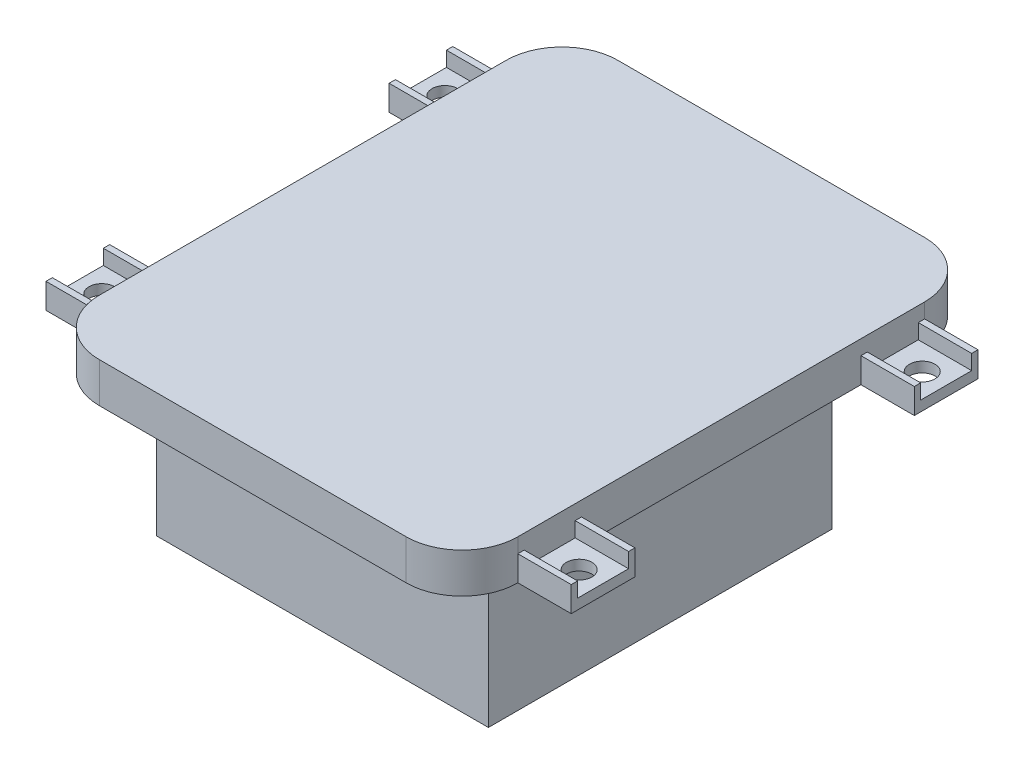
SolidWorks part; units mm, degrees
ref_plane "Front Plane" through (0, 0, 0) normal (0, 0, 1) x (1, 0, 0)
ref_plane "Top Plane" through (0, 0, 0) normal (0, 1, 0) x (1, 0, 0)
ref_plane "Right Plane" through (0, 0, 0) normal (1, 0, 0) x (0, 0, -1)
sketch "Sketch1" plane through (0, 0, 0) normal (0, 1, 0) x (1, 0, 0)
  line L0 (-32.915, 25.49) -> (-32.915, 32.49) construction
  line L1 (-32.915, -32.49) -> (32.915, -32.49) construction
  line L2 (-32.915, 17.51) -> (-32.915, 25.49)
  line L3 (-19.2233, 32.49) -> (32.915, 32.49) construction
  line L4 (32.915, -32.49) -> (32.915, 32.49) construction
  line L5 (-32.915, -32.49) -> (32.915, 32.49) construction
  line L6 (-25.8234, 25.49) -> (32.915, -32.49) construction
  line L7 (-32.915, 17.51) -> (-26.2233, 17.51)
  line L8 (-32.915, 17.51) -> (-32.915, 25.49)
  line L9 (-32.915, 25.49) -> (-26.2233, 25.49)
  line L10 (-26.2233, 17.51) -> (-26.2233, 25.49)
  line L11 (-32.915, 32.49) -> (-25.8234, 25.49) construction
  line L12 (-32.915, 32.49) -> (-19.2233, 32.49) construction
  line L13 (-26.2233, 17.51) -> (-26.2233, -17.51)
  line L14 (-32.915, -32.49) -> (-32.915, 17.51) construction
  line L15 (-19.2233, 32.49) -> (19.2233, 32.49)
  line L16 (0, 0) -> (0, 32.49) construction
  line L17 (0, 0) -> (26.2233, 0) construction
  line L18 (26.2233, 17.51) -> (26.2233, -17.51)
  line L19 (32.915, 25.49) -> (26.2233, 25.49)
  line L20 (26.2233, 17.51) -> (26.2233, 25.49)
  line L21 (32.915, 17.51) -> (26.2233, 17.51)
  line L22 (32.915, 17.51) -> (32.915, 25.49)
  line L23 (32.915, -17.51) -> (32.915, -25.49)
  line L24 (32.915, -25.49) -> (26.2233, -25.49)
  line L25 (32.915, -17.51) -> (26.2233, -17.51)
  line L26 (26.2233, -17.51) -> (26.2233, -25.49)
  line L27 (-19.2233, -32.49) -> (19.2233, -32.49)
  line L28 (-26.2233, -17.51) -> (-26.2233, -25.49)
  line L29 (-32.915, -25.49) -> (-26.2233, -25.49)
  line L30 (-32.915, -17.51) -> (-32.915, -25.49)
  line L31 (-32.915, -17.51) -> (-26.2233, -17.51)
  circle A0 centre (-29.915, 21.5) radius 1.6
  arc A1 (-26.2233, 25.49) -> (-19.2233, 32.49) centre (-19.2233, 25.49) cw
  circle A3 centre (29.915, 21.5) radius 1.6
  arc A5 (26.2233, 25.49) -> (19.2233, 32.49) centre (19.2233, 25.49) ccw
  circle A6 centre (29.915, -21.5) radius 1.6
  arc A8 (26.2233, -25.49) -> (19.2233, -32.49) centre (19.2233, -25.49) cw
  arc A10 (-26.2233, -25.49) -> (-19.2233, -32.49) centre (-19.2233, -25.49) ccw
  circle A11 centre (-29.915, -21.5) radius 1.6
  point P0 (0, 0)
  point P13 (-26.2233, 21.5)
  point P17 (0, 32.49)
  point P27 (0, 32.49)
  point P38 (26.2233, 0)
  point P50 (-26.2233, 0)
  point P51 (25.9556, 0)
  dimension "D3" = 3.2
  dimension "D6" = 7
  dimension "D1" = 65.83
  dimension "D2" = 64.98
  dimension "D4" = 21.5
  dimension "D5" = 29.915
extrude "Boss-Extrude1" add sketch "Sketch1" along normal blind 5 contours L7 L10 L9 L2 A0 | L31 L30 L29 L28 A11 | L28 A10 L27 A8 L26 L18 L20 A5 L15 A1 L10 L13 | L21 L22 L19 L20 A3 | L25 L26 L24 L23 A6 region at (-32.8109, 0, -21.5) region at (0, 0, 0) region at (-26.3275, 0, 21.5) region at (29.5692, 0, -25.3859) region at (26.3275, 0, 21.5)
sketch "Sketch2" plane through (0, 0, 0) normal (0, -1, 0) x (1, 0, 0)
  line L0 (-26.2233, -17.51) -> (-26.2233, 17.51) construction
  line L1 (-22.9942, 21.5394) -> (18.583, 21.5394)
  line L2 (-22.9942, 21.5394) -> (-22.9942, -21.5394)
  line L3 (-22.9942, -21.5394) -> (18.583, -21.5394)
  line L4 (18.583, 21.5394) -> (18.583, -21.5394)
  point P6 (-26.2233, 0)
  point P7 (-22.9942, 0)
extrude "Boss-Extrude2" add sketch "Sketch2" along normal blind 21.5
sketch "Sketch3" plane through (-32.915, 0, 0) normal (-1, 0, 0) x (0, 0, 1)
  line L0 (17.51, 0) -> (25.49, 0) construction
  line L1 (25.49, 0) -> (25.49, 5) construction
  line L2 (25.49, 5) -> (17.51, 5) construction
  line L3 (17.51, 5) -> (17.51, 0) construction
  line L4 (-25.49, 0) -> (-17.51, 0) construction
  line L5 (-17.51, 0) -> (-17.51, 5) construction
  line L6 (-17.51, 5) -> (-25.49, 5) construction
  line L7 (-25.49, 5) -> (-25.49, 0) construction
  line L8 (17.51, 0) -> (25.49, 0)
  line L9 (25.49, 0) -> (25.49, 5)
  line L10 (25.49, 5) -> (17.51, 5)
  line L11 (17.51, 5) -> (17.51, 0)
  line L12 (-25.49, 0) -> (-17.51, 0) construction
  line L13 (-17.51, 1.283) -> (-17.51, 5)
  line L14 (-17.51, 5) -> (-25.49, 5)
  line L15 (-25.49, 5) -> (-25.49, 3.1561)
  line L16 (-25.49, 1.283) -> (-25.49, 0) construction
  line L17 (-25.49, 5) -> (-17.51, 5)
  line L18 (-25.49, 5) -> (-25.49, 3.1561)
  line L19 (-24.6959, 1.283) -> (-18.3041, 1.283)
  line L20 (-17.51, 5) -> (-17.51, 1.283)
  line L21 (-25.49, 1.283) -> (-24.6959, 1.283) construction
  line L22 (-25.49, 1.283) -> (-25.49, 3.1561) construction
  line L23 (-25.49, 3.1561) -> (-24.6959, 3.1561)
  line L24 (-24.6959, 1.283) -> (-24.6959, 3.1561)
  line L25 (-17.51, 1.283) -> (-18.3041, 1.283) construction
  line L26 (-17.51, 1.283) -> (-17.51, 3.1561)
  line L27 (-17.51, 3.1561) -> (-18.3041, 3.1561)
  line L28 (-18.3041, 1.283) -> (-18.3041, 3.1561)
  line L29 (-17.51, 0) -> (-17.51, 1.283) construction
  line L30 (-18.3041, 1.283) -> (-17.51, 1.283) construction
  line L31 (-25.49, 3.1561) -> (-25.49, 1.283) construction
  line L32 (-25.49, 3.1561) -> (-25.49, 1.283) construction
  line L33 (-25.49, 1.283) -> (-24.6959, 1.283) construction
  line L34 (0, -14.575) -> (0, 14.575) construction
  line L35 (18.3041, 1.283) -> (18.3041, 3.1561)
  line L36 (17.51, 3.1561) -> (18.3041, 3.1561)
  line L37 (17.51, 1.283) -> (17.51, 5)
  line L38 (17.51, 5) -> (25.49, 5)
  line L39 (25.49, 5) -> (25.49, 3.1561)
  line L40 (24.6959, 1.283) -> (24.6959, 3.1561)
  line L41 (25.49, 3.1561) -> (24.6959, 3.1561)
  line L42 (24.6959, 1.283) -> (18.3041, 1.283)
  point P16 (0, 0)
  point P17 (0, 0)
  point P18 (-24.6959, 3.1561)
  line M11 (-17.51, 5) -> (-25.49, 5)
  line M12 (-25.49, 5) -> (-25.49, 0)
extrude "Cut-Extrude1" cut sketch "Sketch3" against normal up to vertex (6.6917 mm away) contours L19 L28 L27 L20 L23 L24 M11 M12 | L42 L40 L41 L9 L10 L11 L36 L35 region at (-32.915, 3.2443, 21.5) region at (-32.915, 3.2443, -21.5) up to point (-26.2233, 5, 17.51)
extrude "Cut-Extrude2" cut sketch "Sketch3<3>" against normal up to vertex (65.83 mm away) from vertex contours L19 L28 L27 L20 L23 L24 M11 M12 | L42 L40 L41 L9 L10 L11 L36 L35 region at (-32.915, 3.2443, 21.5) region at (-32.915, 3.2443, -21.5) up to point (32.915, 5, 17.51) starting at point (26.2233, 5, 17.51)
sketch "Sketch3<3>" plane through (-32.915, 0, 0) normal (-1, 0, 0) x (0, 0, 1) same geometry as "Sketch3"
ref_plane "Plane1" through (-2.2056, 0, 0) normal (1, 0, 0) x (0, 0, -1)
sketch "Sketch4" plane through (-2.2056, 0, 0) normal (1, 0, 0) x (0, 0, -1)
  line L0 (32.49, 0) -> (29.4908, 0) construction
  line L1 (25.49, 0) -> (32.49, 0) construction
  line L2 (21.5, 0) -> (21.5394, -4.3232) construction
  line L3 (17.51, 0) -> (25.49, 0) construction
  line L4 (21.5394, -21.5) -> (21.5394, 0) construction
  line L5 (21.5394, -4.3232) -> (29.4908, 0)
  point P11 (29.4908, 0)
  point P12 (21.5394, -6.1769)
  point P13 (21.5, -4.3232)
rib "Rib2" sketch "Sketch4" sketch "Sketch4" thickness 30 extrusion direction parallel to sketch draft on no parameters "D1"=30
mirror "Mirror4" about plane through (0, 0, 0) normal (0, 0, 1) of "Rib2"
